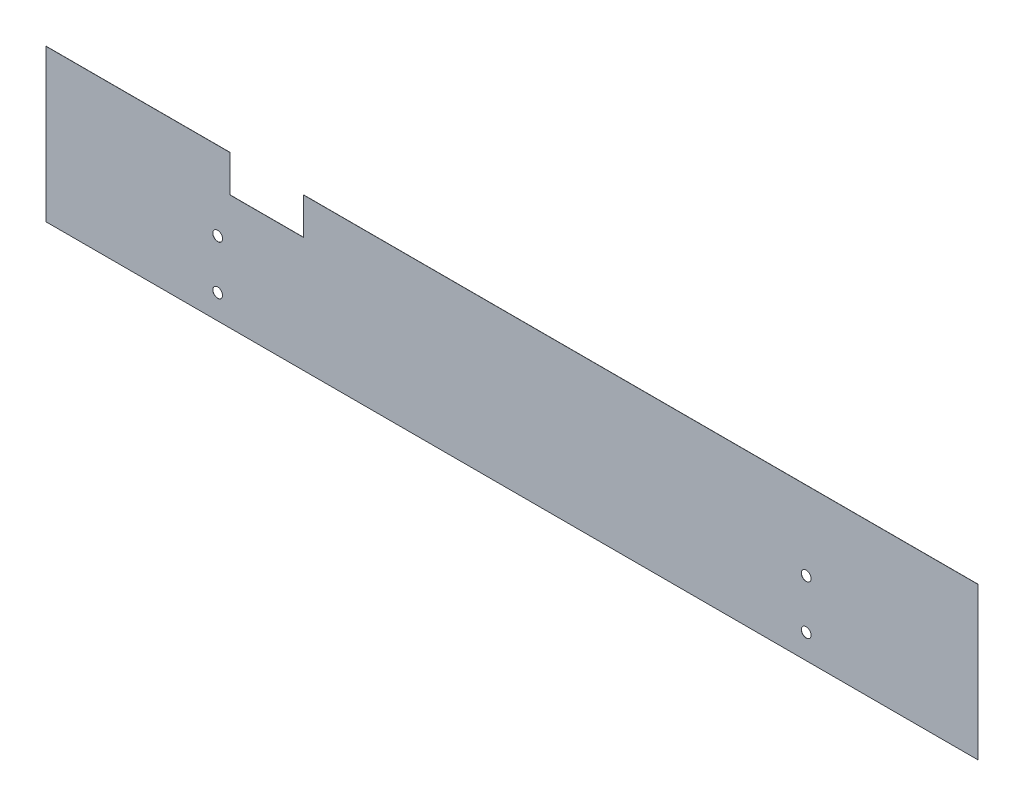
SolidWorks part; units mm, degrees
ref_plane "Front Plane" through (0, 0, 0) normal (0, 0, 1) x (1, 0, 0)
ref_plane "Top Plane" through (0, 0, 0) normal (0, 1, 0) x (1, 0, 0)
ref_plane "Right Plane" through (0, 0, 0) normal (1, 0, 0) x (0, 0, -1)
sketch "Sketch1" plane through (0, 0, 0) normal (0, 0, 1) x (1, 0, 0)
  line L1 (-190, -31) -> (190, -31)
  line L2 (-190, -31) -> (-190, 31)
  line L3 (-190, 31) -> (190, 31)
  line L4 (190, -31) -> (190, 31)
  line L5 (-190, -31) -> (190, 31) construction
  line L6 (-190, 31) -> (190, -31) construction
  point P0 (0, 0)
  dimension "D1" = 380
  dimension "D2" = 62
extrude "Body" add sketch "Sketch1" along normal blind 0.0625
sketch "Sketch2" plane through (0, 0, 0.0625) normal (0, 0, 1) x (1, 0, 0)
  line L0 (-120, -21) -> (120, -21) construction
  line L1 (120, -21) -> (120, -1) construction
  line L2 (120, -1) -> (-120, -1) construction
  line L3 (-120, -1) -> (-120, -21) construction
  line L4 (0, -1) -> (0, -21) construction
  line L6 (-190, -31) -> (190, -31) construction
  line L7 (-190, 31) -> (-190, -31) construction
  circle A0 centre (-120, -1) radius 2
  circle A1 centre (120, -1) radius 2
  circle A2 centre (120, -21) radius 2
  circle A3 centre (-120, -21) radius 2
  point P10 (0, -11)
  point P14 (3.5603, -10.0714)
  dimension "D1" = 4
  dimension "D2" = 20
  dimension "D3" = 10
  dimension "D4" = 70
extrude "Magnetic Holder" cut sketch "Sketch2" against normal blind 0.0625
sketch "Sketch3" plane through (0, 0, 0.0625) normal (0, 0, 1) x (1, 0, 0)
  line L0 (190, 31) -> (-190, 31) construction
  line L1 (-115, 31) -> (-85, 31)
  line L2 (-115, 31) -> (-115, 16)
  line L3 (-115, 16) -> (-85, 16)
  line L4 (-85, 31) -> (-85, 16)
  line L5 (-190, 31) -> (-190, -31) construction
  dimension "D1" = 75
  dimension "D2" = 30
  dimension "D3" = 15
extrude "Cut-Extrude2" cut sketch "Sketch3" against normal blind 0.0625
